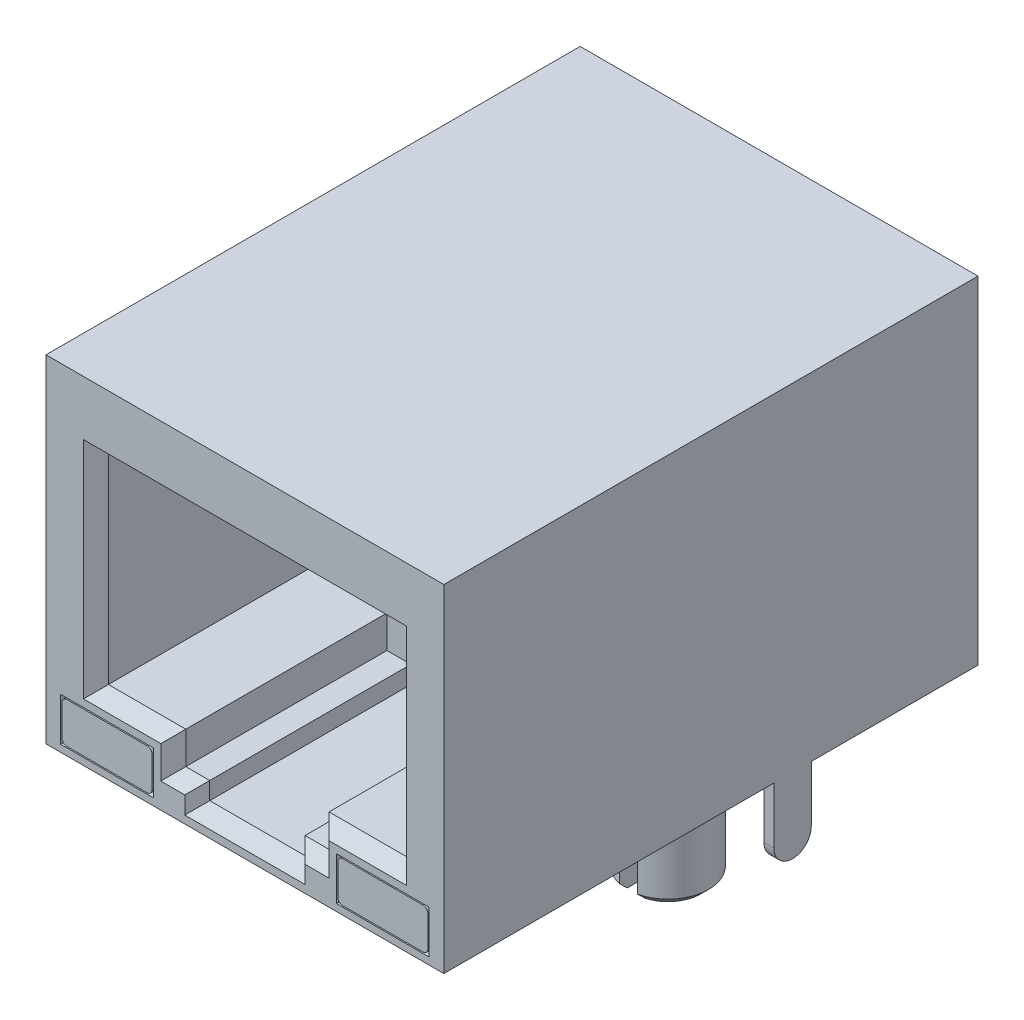
SolidWorks part; units mm, degrees
ref_plane "Front" through (0, 0, 0) normal (0, 0, 1) x (1, 0, 0)
ref_plane "Top" through (0, 0, 0) normal (0, 1, 0) x (1, 0, 0)
ref_plane "Right" through (0, 0, 0) normal (1, 0, 0) x (0, 0, -1)
sketch "Sketch2" plane through (0, 0, 0) normal (0, 1, 0) x (1, 0, 0)
  line L1 (-7.97, 10.7) -> (7.97, 10.7)
  line L2 (-7.97, 10.7) -> (-7.97, -10.7)
  line L3 (-7.97, -10.7) -> (7.97, -10.7)
  line L4 (7.97, 10.7) -> (7.97, -10.7)
  line L5 (-7.97, 10.7) -> (7.97, -10.7) construction
  line L6 (-7.97, -10.7) -> (7.97, 10.7) construction
  point P0 (0, 0)
  dimension "D1" = 21.4
  dimension "D2" = 15.94
extrude "Boss-Extrude1" add sketch "Sketch2" along normal blind 13.5
sketch "Sketch3" plane through (0, 0, 10.7) normal (0, 0, 1) x (1, 0, 0)
  line L0 (-5.97, 10.81) -> (5.97, 10.81)
  line L1 (5.97, 10.81) -> (5.97, 2.81)
  line L2 (5.97, 2.81) -> (2.87, 2.81)
  line L3 (2.87, 2.81) -> (2.87, 1.51)
  line L4 (2.87, 1.51) -> (1.91, 1.51)
  line L5 (1.91, 1.51) -> (1.91, 0.81)
  line L6 (1.91, 0.81) -> (-1.91, 0.81)
  line L7 (-1.91, 0.81) -> (-1.91, 1.51)
  line L8 (-1.91, 1.51) -> (-2.87, 1.51)
  line L9 (-2.87, 1.51) -> (-2.87, 2.81)
  line L10 (-2.87, 2.81) -> (-5.97, 2.81)
  line L11 (-5.97, 2.81) -> (-5.97, 10.81)
  line L12 (-7.97, 13.5) -> (-7.97, 0) construction
  line L13 (7.97, 13.5) -> (7.97, 0) construction
  line L14 (-7.97, 0) -> (7.97, 0) construction
  dimension "D1" = 11.94
  dimension "D2" = 2
  dimension "D3" = 2
  dimension "D4" = 8
  dimension "D5" = 3.1
  dimension "D6" = 1.3
  dimension "D7" = 0.96
  dimension "D8" = 0.7
  dimension "D9" = 0.81
extrude "Cut-Extrude1" cut sketch "Sketch3" against normal blind 8.56
chamfer "Chamfer1" distance 0.5 angle 45 12 edges at (-4.42, 2.81, 10.7) (-2.87, 2.16, 10.7) (-2.39, 1.51, 10.7) (-1.91, 1.16, 10.7) (0, 0.81, 10.7) (1.91, 1.16, 10.7) (2.39, 1.51, 10.7) (2.87, 2.16, 10.7) (4.42, 2.81, 10.7) (5.97, 6.81, 10.7) (-5.97, 6.81, 10.7) (0, 10.81, 10.7)
sketch "Sketch4" plane through (0, 0, 10.7) normal (0, 0, 1) x (1, 0, 0)
  line L0 (0, 0) -> (0, 14.1602) construction
  line L1 (-2.87, 2.81) -> (-2.87, 1.51) construction
  line L2 (-7.38, 2.01) -> (-3.67, 2.01)
  line L3 (-7.38, 2.01) -> (-7.38, 0.28)
  line L4 (-7.38, 0.28) -> (-3.67, 0.28)
  line L5 (-3.67, 2.01) -> (-3.67, 0.28)
  line L6 (-7.38, 2.01) -> (-3.67, 0.28) construction
  line L7 (-7.38, 0.28) -> (-3.67, 2.01) construction
  line L8 (-3.37, 2.31) -> (-6.47, 2.31) construction
  line L9 (7.38, 0.28) -> (3.67, 2.01) construction
  line L10 (7.38, 2.01) -> (3.67, 0.28) construction
  line L11 (3.67, 2.01) -> (3.67, 0.28)
  line L12 (7.38, 0.28) -> (3.67, 0.28)
  line L13 (7.38, 2.01) -> (7.38, 0.28)
  line L14 (7.38, 2.01) -> (3.67, 2.01)
  point P3 (-5.525, 1.145)
  point P16 (5.525, 1.145)
  dimension "D1" = 3.71
  dimension "D2" = 1.73
  dimension "D3" = 0.8
  dimension "D4" = 0.3
extrude "Cut-Extrude2" cut sketch "Sketch4" against normal blind 8
sketch "Sketch5" plane through (0, 0, 2.7) normal (0, 0, 1) x (1, 0, 0)
  line L1 (-5.525, 2.01) -> (-5.525, 0.28) construction
  line L2 (-3.67, 2.01) -> (-7.38, 2.01) construction
  line L3 (-7.38, 0.28) -> (-3.67, 0.28) construction
  line L4 (-7.38, 1.145) -> (-3.67, 1.145) construction
  line L5 (-7.38, 2.01) -> (-7.38, 0.28) construction
  line L6 (-3.67, 0.28) -> (-3.67, 2.01) construction
  line L8 (0, 0) -> (0, 19.2264) construction
  line L9 (-7.13, 1.96) -> (-3.92, 1.96)
  line L10 (-7.33, 1.76) -> (-7.33, 0.53)
  line L11 (-7.13, 0.33) -> (-3.92, 0.33)
  line L12 (-3.72, 1.76) -> (-3.72, 0.53)
  line L13 (-7.33, 1.96) -> (-3.72, 0.33) construction
  line L14 (-7.33, 0.33) -> (-3.72, 1.96) construction
  line L15 (3.72, 1.76) -> (3.72, 0.53)
  line L16 (7.13, 0.33) -> (3.92, 0.33)
  line L17 (7.33, 1.76) -> (7.33, 0.53)
  line L18 (7.13, 1.96) -> (3.92, 1.96)
  arc A0 (-7.13, 1.96) -> (-7.33, 1.76) centre (-7.13, 1.76) ccw
  arc A1 (-7.33, 0.53) -> (-7.13, 0.33) centre (-7.13, 0.53) ccw
  arc A2 (-3.92, 0.33) -> (-3.72, 0.53) centre (-3.92, 0.53) ccw
  arc A3 (-3.92, 1.96) -> (-3.72, 1.76) centre (-3.92, 1.76) cw
  arc A4 (3.72, 0.53) -> (3.92, 0.33) centre (3.92, 0.53) ccw
  arc A5 (7.13, 0.33) -> (7.33, 0.53) centre (7.13, 0.53) ccw
  arc A6 (7.33, 1.76) -> (7.13, 1.96) centre (7.13, 1.76) ccw
  arc A7 (3.72, 1.76) -> (3.92, 1.96) centre (3.92, 1.76) cw
  point P12 (-5.525, 1.145)
  point P38 (3.72, 0.33)
  point P41 (7.33, 0.33)
  point P44 (7.33, 1.96)
  point P47 (3.72, 1.96)
  dimension "D3" = 0.2
  dimension "D4" = 0.2
  dimension "D5" = 0.2
  dimension "D1" = 0.05
  dimension "D2" = 0.05
extrude "Boss-Extrude2" add sketch "Sketch5" along normal blind 8
ref_plane "Plane1" through (3.47, 0, 0) normal (-1, 0, 0) x (0, 0, 1)
sketch "Sketch6" plane through (3.47, 0, 0) normal (-1, 0, 0) x (0, 0, 1)
  line L0 (9.1573, 10.8042) -> (9.1573, 10.6239)
  line L2 (8.911, 10.3287) -> (2.14, 9.0968)
  line L3 (2.14, 10.81) -> (2.14, 2.81) construction
  line L4 (2.14, 9.0968) -> (2.14, 9.5275)
  line L5 (2.14, 9.5275) -> (9.1573, 10.8042)
  arc A0 (9.1573, 10.6239) -> (8.911, 10.3287) centre (8.8573, 10.6239) cw
  dimension "D1" = 0.3
extrude "Boss-Extrude5" add sketch "Sketch6" along normal mid plane 0.5
pattern_linear "LPattern1" count 8 spacing 1 along (-1, 0, 0) of "Boss-Extrude5"
sketch "Sketch8" plane through (0, 0, 0) normal (1, 0, 0) x (0, 0, -1)
  line L0 (4.02, 0) -> (4.02, -2.25)
  line L1 (-10.7, 0) -> (10.7, 0) construction
  line L2 (2.52, -2.25) -> (2.52, 0)
  line L3 (2.52, 0) -> (4.02, 0)
  arc A0 (4.02, -2.25) -> (2.52, -2.25) centre (3.27, -2.25) cw
  dimension "D3" = 0.75
  dimension "D1" = 13.22
  dimension "D2" = 2.25
extrude "Boss-Extrude7" add sketch "Sketch8" against normal blind 0.4 from offset 7.97
extrude "Boss-Extrude8" add sketch "Sketch8<2>" along normal blind 0.4 from offset 7.97 offset against normal yes
sketch "Sketch8<2>" plane through (0, 0, 0) normal (1, 0, 0) x (0, 0, -1) same geometry as "Sketch8"
sketch "Sketch9" plane through (0, 0, 0) normal (0, -1, 0) x (1, 0, 0)
  line L0 (-7.97, 10.7) -> (7.97, 10.7) construction
  line L1 (0, 12.0129) -> (0, -12.0129) construction
  line L2 (-7.97, -2.52) -> (-7.97, 10.7) construction
  circle A0 centre (6.0306, -0.22) radius 1.625
  circle A1 centre (-6.0306, -0.22) radius 1.625
  point P10 (0, 0)
  dimension "D1" = 1.9394
  dimension "D2" = 3.25
  dimension "D3" = 10.92
extrude "Boss-Extrude9" add sketch "Sketch9" along normal blind 3
sketch "Sketch10" plane through (0, 0, 0) normal (0, -1, 0) x (1, 0, 0)
  line L0 (-6.0306, 1.405) -> (-6.0306, -1.845) construction
  line L1 (-6.3875, 1.5255) -> (-5.6738, 1.5255)
  line L2 (-6.3875, 1.5255) -> (-6.3875, -2.0579)
  line L3 (-6.3875, -2.0579) -> (-5.6738, -2.0579)
  line L4 (-5.6738, 1.5255) -> (-5.6738, -2.0579)
  line L5 (0, 14.4692) -> (0, -14.4692) construction
  line L6 (-6.3875, 1.5255) -> (-6.3875, -2.0579)
  line L7 (-5.6738, 1.5255) -> (-5.6738, -2.0579)
  line L8 (6.0306, 1.405) -> (6.0306, -1.845) construction
  line L9 (5.6738, 1.5255) -> (5.6738, -2.0579)
  line L10 (6.3875, 1.5255) -> (6.3875, -2.0579)
  line L11 (5.6738, 1.5255) -> (5.6738, -2.0579)
  line L12 (6.3875, -2.0579) -> (5.6738, -2.0579)
  line L13 (6.3875, 1.5255) -> (6.3875, -2.0579)
  line L14 (6.3875, 1.5255) -> (5.6738, 1.5255)
  circle A0 centre (-6.0306, -0.22) radius 1.625 construction
  circle A1 centre (-6.0306, -0.22) radius 1.625 construction
  point P15 (0, 0)
  circle M7 centre (-6.0306, -0.22) radius 1.625
  circle M8 centre (6.0306, -0.22) radius 1.625
extrude "Cut-Extrude3" cut sketch "Sketch10" along normal blind 3 contours L4 L2 M7 | L10 L9 M8 region at (-6.0306, 0, -0.22) region at (6.0306, 0, -0.22)
chamfer "Chamfer2" distance 0.3 angle 45 4 edges at (7.6556, -3, -0.22) (4.4056, -3, -0.22) (-4.4056, -3, -0.22) (-7.6556, -3, -0.22)
sketch "Sketch11" plane through (0, 0, 0) normal (0, -1, 0) x (1, 0, 0)
  line L0 (-6.3875, 1.056) -> (-6.3875, -1.496) construction
  line L1 (7.97, -10.7) -> (-7.97, -10.7) construction
  circle A0 centre (-5.0134, -9.11) radius 0.445
  circle A1 centre (-2.4734, -9.11) radius 0.445
  circle A2 centre (0.0666, -9.11) radius 0.445
  circle A3 centre (2.6066, -9.11) radius 0.445
  circle A4 centre (-3.7191, -6.57) radius 0.445
  circle A5 centre (-1.1791, -6.57) radius 0.445
  circle A6 centre (1.3609, -6.57) radius 0.445
  circle A7 centre (3.9009, -6.57) radius 0.445
  point P2 (-6.3875, -0.22)
  dimension "D1" = 0.89
  dimension "D5" = 0.89
  dimension "D2" = 8.89
  dimension "D3" = 1.59
  dimension "D6" = 2.54
  dimension "D4" = 4
extrude "Boss-Extrude10" add sketch "Sketch11" along normal blind 3
chamfer "Chamfer3" distance 0.15 angle 45 8 edges at (3.9009, -3, -7.015) (2.6066, -3, -9.555) (1.3609, -3, -7.015) (0.0666, -3, -9.555) (-1.1791, -3, -7.015) (-2.4734, -3, -9.555) (-3.7191, -3, -7.015) (-5.0134, -3, -9.555)
